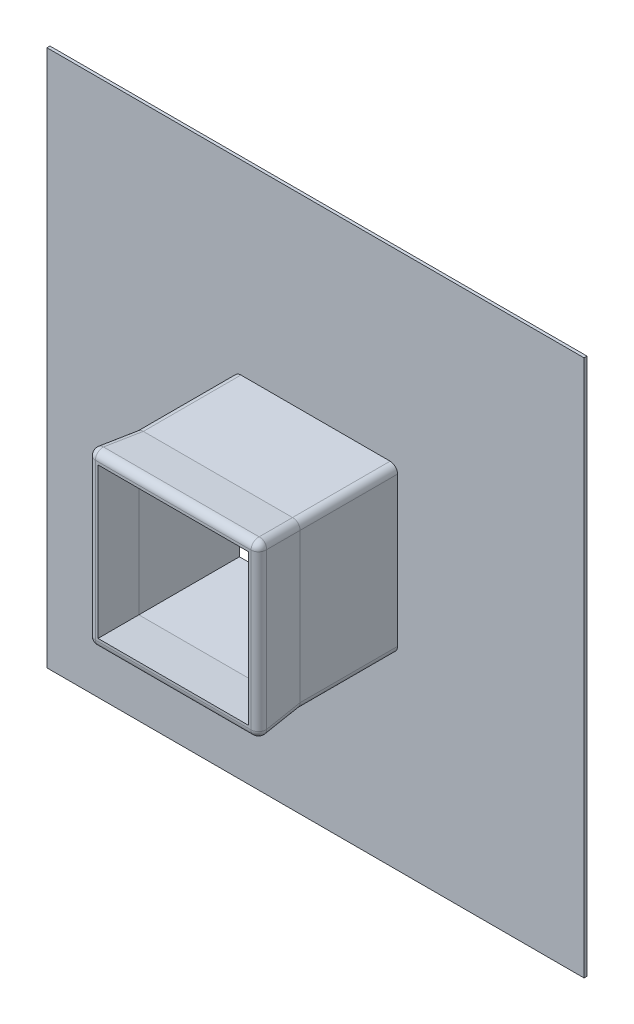
SolidWorks part; units mm, degrees
ref_plane "前视基准面" through (0, 0, 0) normal (0, 0, 1) x (1, 0, 0)
ref_plane "上视基准面" through (0, 0, 0) normal (0, 1, 0) x (1, 0, 0)
ref_plane "右视基准面" through (0, 0, 0) normal (1, 0, 0) x (0, 0, -1)
sketch "草图2" plane through (0, 0, 36.2643) normal (0, 0, 1) x (1, 0, 0)
  line L1 (-9.3862, -9.3862) -> (350.6138, -9.3862)
  line L2 (-9.3862, -9.3862) -> (-9.3862, 350.6138)
  line L3 (-9.3862, 350.6138) -> (350.6138, 350.6138)
  line L4 (350.6138, -9.3862) -> (350.6138, 350.6138)
extrude "凸台-拉伸1" add sketch "草图2" along normal blind 2
sketch "草图3" plane through (0, 0, 38.2643) normal (0, 0, 1) x (1, 0, 0)
  line L7 (115.6138, 225.6138) -> (225.6138, 225.6138)
  line L8 (115.6138, 225.6138) -> (115.6138, 115.6138)
  line L9 (115.6138, 115.6138) -> (225.6138, 115.6138)
  line L11 (225.6138, 225.6138) -> (225.6138, 115.6138)
  line L12 (115.6138, 225.6138) -> (225.6138, 115.6138) construction
  line L13 (115.6138, 115.6138) -> (225.6138, 225.6138) construction
  point P0 (170.6138, 170.6138)
  point P2 (250.6138, 170.6138)
  dimension "D1" = 110
extrude "切除-拉伸1" cut sketch "草图3" against normal blind 75
sketch "草图4" plane through (0, 0, 36.2643) normal (0, 0, -1) x (-1, 0, 0)
  line L1 (-225.6138, 115.6138) -> (-115.6138, 115.6138)
  line L2 (-225.6138, 115.6138) -> (-225.6138, 225.6138)
  line L3 (-225.6138, 225.6138) -> (-115.6138, 225.6138)
  line L4 (-115.6138, 115.6138) -> (-115.6138, 225.6138)
  line L5 (-225.6138, 115.6138) -> (-115.6138, 225.6138) construction
  line L6 (-225.6138, 225.6138) -> (-115.6138, 115.6138) construction
  line L7 (-115.6138, 225.6138) -> (-115.6138, 115.6138) construction
  line L8 (-223.6138, 117.6138) -> (-117.6138, 117.6138)
  line L9 (-117.6138, 117.6138) -> (-117.6138, 223.6138)
  line L10 (-223.6138, 223.6138) -> (-117.6138, 223.6138)
  line L11 (-223.6138, 117.6138) -> (-223.6138, 223.6138)
  point P0 (-170.6138, 170.6138)
  dimension "D1" = 110
  dimension "D2" = 2
extrude "凸台-拉伸2" add sketch "草图4" against normal up to surface (67.3945 mm away)
sketch "草图5" plane through (0, 0, 103.6589) normal (0, 0, 1) x (1, 0, 0)
  line L0 (223.6138, 117.6138) -> (223.6138, 223.6138) construction
  line L1 (223.6138, 117.6138) -> (223.6138, 223.6138)
  line L2 (117.6138, 117.6138) -> (223.6138, 117.6138) construction
  line L3 (117.6138, 117.6138) -> (223.6138, 117.6138)
  line L4 (115.6138, 225.6138) -> (115.6138, 115.6138)
  line L5 (115.6138, 115.6138) -> (225.6138, 115.6138)
  line L6 (225.6138, 115.6138) -> (225.6138, 225.6138)
  line L7 (225.6138, 225.6138) -> (115.6138, 225.6138)
  line L8 (115.6138, 225.6138) -> (115.6138, 115.6138)
  line L9 (115.6138, 115.6138) -> (225.6138, 115.6138)
  line L10 (225.6138, 115.6138) -> (225.6138, 225.6138)
  line L11 (225.6138, 225.6138) -> (115.6138, 225.6138)
  line L12 (117.6138, 223.6138) -> (117.6138, 117.6138) construction
  line L13 (117.6138, 223.6138) -> (117.6138, 117.6138)
  line L14 (223.6138, 223.6138) -> (117.6138, 223.6138) construction
  line L15 (223.6138, 223.6138) -> (117.6138, 223.6138)
  dimension "D1" = 0
extrude "凸台-拉伸3" add sketch "草图5" along normal blind 30 draft 5 draft outward yes
fillet "圆角1" radius 5 8 edges at (226.9261, 226.9261, 118.6589) (226.9261, 114.3014, 118.6589) (114.3014, 114.3014, 118.6589) (114.3014, 226.9261, 118.6589) (228.2384, 170.6138, 133.6589) (170.6138, 228.2384, 133.6589) (112.9891, 170.6138, 133.6589) (170.6138, 112.9891, 133.6589)
fillet "圆角2" radius 5 4 edges at (225.6138, 225.6138, 79.2862) (115.6138, 225.6138, 79.2862) (225.6138, 115.6138, 79.2862) (115.6138, 115.6138, 79.2862)
